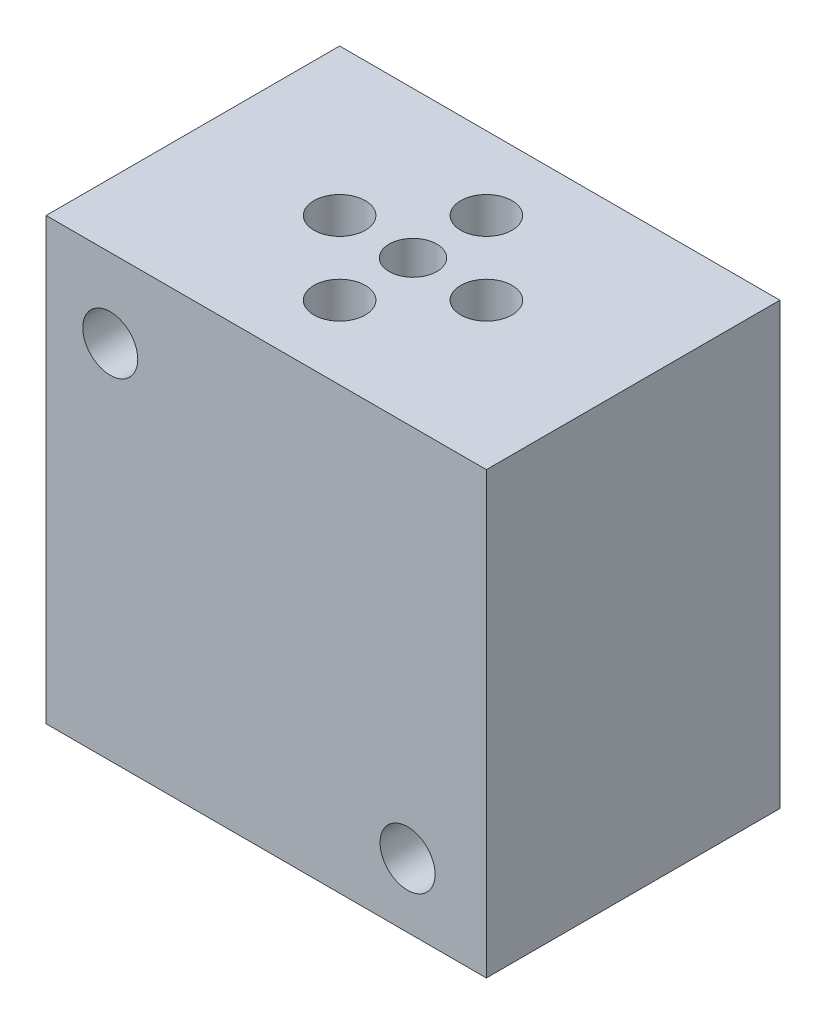
SolidWorks part; units mm, degrees
ref_plane "Front Plane" through (0, 0, 0) normal (0, 0, 1) x (1, 0, 0)
ref_plane "Top Plane" through (0, 0, 0) normal (0, 1, 0) x (1, 0, 0)
ref_plane "Right Plane" through (0, 0, 0) normal (1, 0, 0) x (0, 0, -1)
sketch "Sketch3" plane through (0, 0, 0) normal (0, 1, 0) x (1, 0, 0)
  line L1 (-40.3412, 23.5946) -> (35.8588, 23.5946)
  line L2 (-40.3412, 23.5946) -> (-40.3412, -27.2054)
  line L3 (-40.3412, -27.2054) -> (35.8588, -27.2054)
  line L4 (35.8588, 23.5946) -> (35.8588, -27.2054)
  dimension "D1" = 50.8
  dimension "D2" = 76.2
extrude "Boss-Extrude1" add sketch "Sketch3" along normal blind 76.2
sketch "Sketch5" plane through (0, 76.2, 0) normal (0, 1, 0) x (1, 0, 0)
  line L0 (-40.3412, 23.5946) -> (-40.3412, -27.2054) construction
  line L1 (-40.3412, -27.2054) -> (35.8588, -27.2054) construction
  circle A0 centre (-2.2412, -1.8054) radius 4.1275
  dimension "D3" = 8.255
  dimension "D1" = 38.1
  dimension "D2" = 25.4
extrude "Cut-Extrude1" cut sketch "Sketch5" against normal blind 76.2
sketch "Sketch6" plane through (0, 76.2, 0) normal (0, 1, 0) x (1, 0, 0)
  line L0 (35.8588, 23.5946) -> (-40.3412, 23.5946) construction
  line L1 (-40.3412, 23.5946) -> (-40.3412, -27.2054) construction
  circle A0 centre (-14.9412, -1.8054) radius 4.445
  dimension "D1" = 8.89
  dimension "D2" = 25.4
  dimension "D3" = 25.4
extrude "Cut-Extrude2" cut sketch "Sketch6" against normal blind 76.2
sketch "Sketch8" plane through (0, 76.2, 0) normal (0, 1, 0) x (1, 0, 0)
  line L2 (-40.3412, -27.2054) -> (35.8588, -27.2054) construction
  line L3 (35.8588, -27.2054) -> (35.8588, 23.5946) construction
  circle A0 centre (10.4588, -1.8054) radius 4.445
  dimension "D1" = 8.89
  dimension "D2" = 25.4
  dimension "D3" = 25.4
extrude "Cut-Extrude4" cut sketch "Sketch8" against normal blind 76.2
sketch "Sketch9" plane through (0, 76.2, 0) normal (0, 1, 0) x (1, 0, 0)
  line L2 (-40.3412, -27.2054) -> (35.8588, -27.2054) construction
  line L3 (-40.3412, 23.5946) -> (-40.3412, -27.2054) construction
  circle A0 centre (-2.2412, -14.5054) radius 4.445
  dimension "D1" = 8.89
  dimension "D2" = 12.7
  dimension "D3" = 38.1
extrude "Cut-Extrude5" cut sketch "Sketch9" against normal blind 76.2
sketch "Sketch10" plane through (0, 76.2, 0) normal (0, 1, 0) x (1, 0, 0)
  line L2 (-40.3412, 23.5946) -> (-40.3412, -27.2054) construction
  line L3 (35.8588, 23.5946) -> (-40.3412, 23.5946) construction
  circle A0 centre (-2.2412, 10.8946) radius 4.445
  dimension "D1" = 8.89
  dimension "D2" = 38.1
  dimension "D3" = 12.7
extrude "Cut-Extrude6" cut sketch "Sketch10" against normal blind 76.2
sketch "Sketch12" plane through (0, 0, 27.2054) normal (0, 0, 1) x (1, 0, 0)
  line L0 (-40.3412, 76.2) -> (-40.3412, 0) construction
  line L1 (-40.3412, 76.2) -> (35.8588, 76.2) construction
  circle A0 centre (-29.2414, 62.5602) radius 4.7625
  dimension "D1" = 9.525
  dimension "D2" = 11.0998
  dimension "D3" = 13.6398
extrude "Cut-Extrude7" cut sketch "Sketch12" against normal blind 76.2
sketch "Sketch13" plane through (0, 0, 27.2054) normal (0, 0, 1) x (1, 0, 0)
  line L2 (-40.3412, 0) -> (35.8588, 0) construction
  line L3 (35.8588, 76.2) -> (35.8588, 0) construction
  circle A0 centre (22.219, 11.0998) radius 4.7625
  circle A1 centre (-29.2414, 62.5602) radius 4.7625 construction
  circle A2 centre (-29.2414, 62.5602) radius 4.7625
  point P6 (0, 0)
  point P10 (0, 0)
  dimension "D1" = 9.525
  dimension "D2" = 11.0998
  dimension "D3" = 13.6398
  dimension "D4" = 72.776
extrude "Cut-Extrude8" cut sketch "Sketch13" against normal blind 76.2
